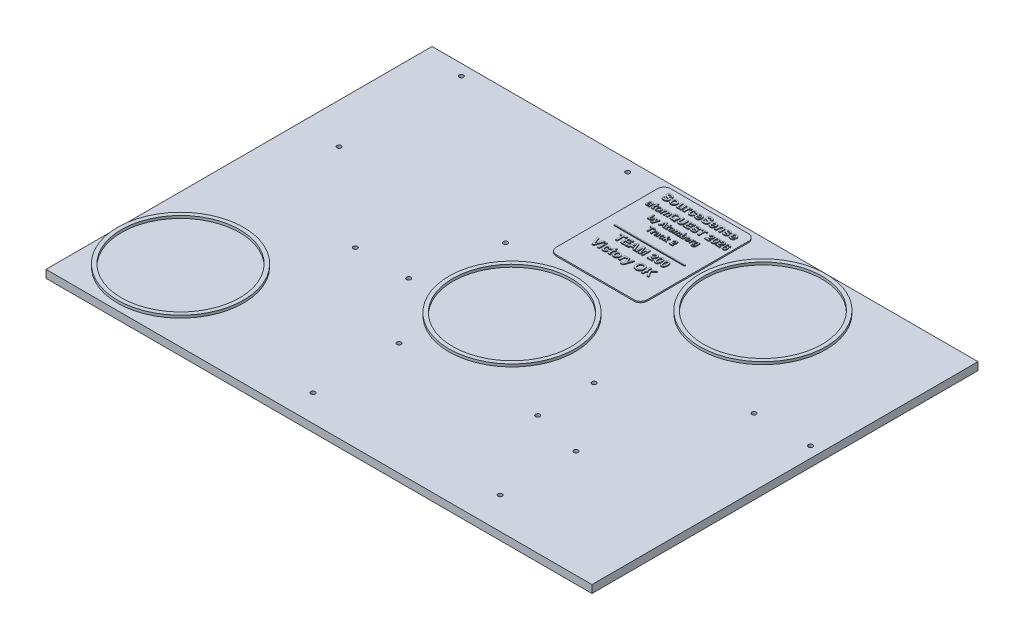
SolidWorks part; units mm, degrees
material "PMMA"
ref_plane "Front Plane" through (0, 0, 0) normal (0, 0, 1) x (1, 0, 0)
ref_plane "Top Plane" through (0, 0, 0) normal (0, 1, 0) x (1, 0, 0)
ref_plane "Right Plane" through (0, 0, 0) normal (1, 0, 0) x (0, 0, -1)
other "Configuration Table"
sketch "Sketch1" plane through (0, 0, 0) normal (0, 1, 0) x (1, 0, 0)
  line L1 (-210, -148.5) -> (210, -148.5)
  line L2 (-210, -148.5) -> (-210, 148.5)
  line L3 (-210, 148.5) -> (210, 148.5)
  line L4 (210, -148.5) -> (210, 148.5)
  line L5 (-210, -148.5) -> (210, 148.5) construction
  line L6 (-210, 148.5) -> (210, -148.5) construction
  point P6 (0, 0)
  dimension "D1" = 420
  dimension "D2" = 297
extrude "Plate" add sketch "Sketch1" along normal blind 6
sketch "Sketch2" plane through (0, 0, 0) normal (0, 1, 0) x (1, 0, 0)
  circle A0 centre (-25, -62) radius 1.65
  circle A1 centre (-25, -128) radius 1.65
  circle A2 centre (-105.5, -15) radius 1.65
  circle A3 centre (-64.5, -15) radius 1.65
  circle A4 centre (-179, 140) radius 1.65
  circle A5 centre (-179, 46) radius 1.65
  circle A6 centre (-51, 140) radius 1.65
  circle A7 centre (-51, 46) radius 1.65
  circle A8 centre (115, -65.8) radius 1.65
  circle A9 centre (115, -124.2) radius 1.65
  circle A10 centre (158.3, 28) radius 1.65
  circle A11 centre (201.7, 28) radius 1.65
  circle A12 centre (76.5, -13.3) radius 1.65
  circle A13 centre (76.5, -56.7) radius 1.65
  dimension "D1" = 3.3
  dimension "D2" = 3.3
  dimension "D3" = 3.3
  dimension "D4" = 3.3
  dimension "D5" = 3.3
  dimension "D6" = 3.3
  dimension "D7" = 3.3
  dimension "D8" = 3.3
  dimension "D9" = 3.3
  dimension "D10" = 3.3
  dimension "D11" = 3.3
  dimension "D12" = 3.3
  dimension "D13" = 3.3
  dimension "D14" = 3.3
extrude "Tapped_Holes_M4" cut sketch "Sketch2" along normal through all and the other way through all
sketch "Sketch3" plane through (0, 0, 0) normal (0, 1, 0) x (1, 0, 0)
  circle A0 centre (-160, -95) radius 45.5
  circle A1 centre (-160, -95) radius 48.5
  circle A2 centre (0, 0) radius 45.5
  circle A3 centre (0, 0) radius 48.5
  circle A4 centre (95, 98) radius 45.5
  circle A5 centre (95, 98) radius 48.5
  dimension "D1" = 91
  dimension "D2" = 97
  dimension "D3" = 91
  dimension "D4" = 97
  dimension "D5" = 91
  dimension "D6" = 97
extrude "Jar_Locating_Rings" add sketch "Sketch3" along normal blind 2 from offset 6
sketch "Sketch4" plane through (0, 0, 0) normal (0, 1, 0) x (1, 0, 0)
  line L0 (-22.5, 56.5) -> (37.5, 56.5)
  line L1 (42.5, 61.5) -> (42.5, 139.5)
  line L2 (37.5, 144.5) -> (-22.5, 144.5)
  line L3 (-27.5, 139.5) -> (-27.5, 61.5)
  arc A0 (37.5, 56.5) -> (42.5, 61.5) centre (37.5, 61.5) ccw
  arc A1 (42.5, 139.5) -> (37.5, 144.5) centre (37.5, 139.5) ccw
  arc A2 (-22.5, 144.5) -> (-27.5, 139.5) centre (-22.5, 139.5) ccw
  arc A3 (-27.5, 61.5) -> (-22.5, 56.5) centre (-22.5, 61.5) ccw
extrude "Team_Badge" add sketch "Sketch4" along normal blind 1 from offset 6
sketch "Sketch5" plane through (0, 0, 0) normal (0, 1, 0) x (1, 0, 0)
  line L0 (-19.5, 98.1) -> (34.5, 98.1)
  line L1 (34.5, 98.1) -> (34.5, 98.9)
  line L2 (34.5, 98.9) -> (-19.5, 98.9)
  line L3 (-19.5, 98.9) -> (-19.5, 98.1)
  text T0 "SourceSense" font "Arial" height 6.5
  text T1 "atomQUEST 2026" font "Arial" height 5.4
  text T2 "by Atomberg" font "Arial" height 4.5
  text T3 "Track 2" font "Arial" height 4.5
  text T4 "TEAM 200" font "Arial" height 6
  text T5 "Victory OK" font "Arial" height 6.5
extrude "Badge_Text" add sketch "Sketch5" along normal blind 0.6 from offset 7
equation "\"Jar_OD\"= 90  'ASSUMED - Part C fallback - jar outer diameter"
equation "\"Jar_H\"= 120  'ASSUMED - Part C fallback - jar height"
equation "\"Pump_L\"= 45  'ASSUMED - Part C fallback"
equation "\"Pump_W\"= 24  'ASSUMED - Part C fallback"
equation "\"Pump_H\"= 33  'ASSUMED - Part C fallback"
equation "\"Pump_Outlet_OD\"= 7.5  'ASSUMED - Part C fallback"
equation "\"Tube_OD\"= 8  'ASSUMED - Part C fallback"
equation "\"Tube_ID\"= 6  'ASSUMED - Part C fallback"
equation "\"TDS_Body_Dia\"= 12  'ASSUMED - Part C fallback"
equation "\"TDS_Wet_Len\"= 45  'ASSUMED - Part C fallback - length in water"
equation "\"DS_Tube_Dia\"= 6  'ASSUMED - Part C fallback"
equation "\"DS_Tube_Len\"= 50  'ASSUMED - Part C fallback"
equation "\"ORP_Body_Dia\"= 12  'ASSUMED - Part C fallback"
equation "\"ORP_Body_Len\"= 150  'ASSUMED - Part C fallback"
equation "\"ORP_Cap_Dia\"= 16  'ASSUMED - Part C fallback"
equation "\"Turb_W\"= 33  'ASSUMED - Part C fallback - head width"
equation "\"Turb_D\"= 28  'ASSUMED - Part C fallback - head depth"
equation "\"Turb_H\"= 30  'ASSUMED - Part C fallback - head height"
equation "\"Turb_Slot_W\"= 10  'ASSUMED - Part C fallback - slot width"
equation "\"Flow_L\"= 62  'ASSUMED - Part C fallback YF-S201"
equation "\"Flow_W\"= 36  'ASSUMED - Part C fallback"
equation "\"Flow_H\"= 35  'ASSUMED - Part C fallback"
equation "\"Thread_G12_OD\"= 20.955  'ASSUMED - Part C fallback thread G1/2 (major diameter)"
equation "\"Valve_L\"= 75  'ASSUMED - Part C fallback"
equation "\"Valve_W\"= 45  'ASSUMED - Part C fallback"
equation "\"Valve_H\"= 60  'ASSUMED - Part C fallback"
equation "\"Tee_L\"= 40  'ASSUMED - Part C fallback - overall length"
equation "\"Tee_Branch_L\"= 25  'ASSUMED - Part C fallback"
equation "\"Tee_OD\"= 12  'ASSUMED - Part C fallback"
equation "\"Cuv_W\"= 12.5  'ASSUMED - Part C fallback"
equation "\"Cuv_D\"= 12.5  'ASSUMED - Part C fallback"
equation "\"Cuv_H\"= 45  'ASSUMED - Part C fallback"
equation "\"LED_Board_L\"= 20  'ASSUMED - Part C fallback"
equation "\"LED_Board_W\"= 20  'ASSUMED - Part C fallback - LED at centre"
equation "\"GUVA_L\"= 20  'ASSUMED - Part C fallback"
equation "\"GUVA_W\"= 12  'ASSUMED - Part C fallback - sensor at centre"
equation "\"Reed_L\"= 27  'ASSUMED - Part C fallback MC-38 half"
equation "\"Reed_W\"= 14  'ASSUMED - Part C fallback"
equation "\"Reed_H\"= 8  'ASSUMED - Part C fallback"
equation "\"ESP_L\"= 51  'ASSUMED - Part C fallback"
equation "\"ESP_W\"= 28  'ASSUMED - Part C fallback"
equation "\"TFT_L\"= 58  'ASSUMED - Part C fallback - board"
equation "\"TFT_W\"= 35  'ASSUMED - Part C fallback - board"
equation "\"TFT_Win_L\"= 35  'ASSUMED - Part C fallback - visible window"
equation "\"TFT_Win_W\"= 28  'ASSUMED - Part C fallback - visible window"
equation "\"Relay_L\"= 50  'ASSUMED - Part C fallback"
equation "\"Relay_W\"= 26  'ASSUMED - Part C fallback"
equation "\"Relay_H\"= 19  'ASSUMED - Part C fallback"
equation "\"Mosfet_L\"= 34  'ASSUMED - Part C fallback"
equation "\"Mosfet_W\"= 17  'ASSUMED - Part C fallback"
equation "\"Mosfet_H\"= 12  'ASSUMED - Part C fallback"
equation "\"TDS_Board_L\"= 42  'ASSUMED - Part C fallback"
equation "\"TDS_Board_W\"= 32  'ASSUMED - Part C fallback"
equation "\"Turb_Board_L\"= 38  'ASSUMED - Part C fallback"
equation "\"Turb_Board_W\"= 28  'ASSUMED - Part C fallback"
equation "\"BNC_Thread_Dia\"= 9.5  'ASSUMED - Part C fallback"
equation "\"Plate_L\"= 420  'ASSUMED - Part C fallback"
equation "\"Plate_W\"= 297  'ASSUMED - Part C fallback"
equation "\"Plate_T\"= 6  'ASSUMED - Part C fallback"
equation "\"Probe_Clr\"= 0.3  'DESIGN VALUE - Part C rule 3 - printed probe hole = diameter + 0.3"
equation "\"Cuv_Clr\"= 0.2  'DESIGN VALUE - Part C rule 3 - cuvette pocket = size + 0.2"
equation "\"Label_H\"= 0.6  'DESIGN VALUE - Part D - raised label height"
equation "\"D1@Sketch1\" = \"Plate_L\""
equation "\"D2@Sketch1\" = \"Plate_W\""
equation "\"D1@Plate\" = \"Plate_T\""
